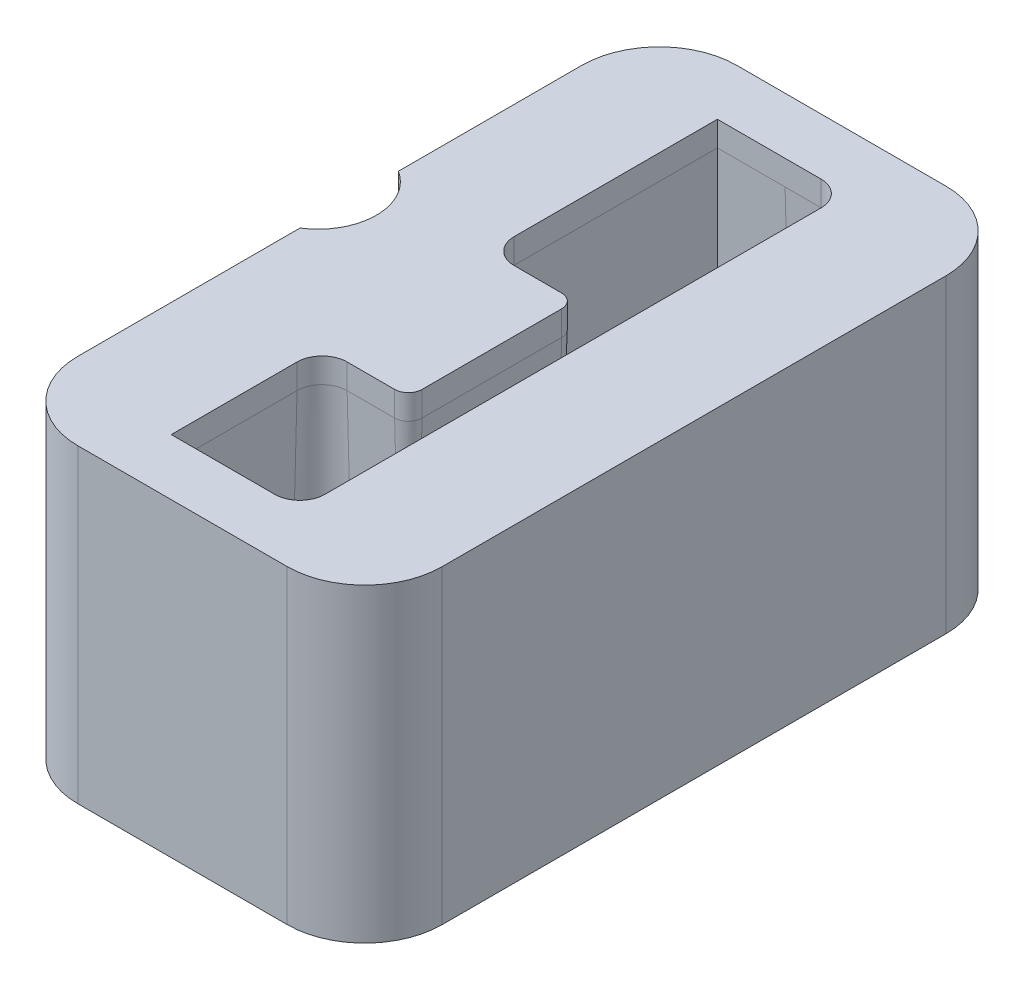
SolidWorks part; units mm, degrees
material "K110"
ref_plane "Front Plane" through (0, 0, 0) normal (0, 0, 1) x (1, 0, 0)
ref_plane "Top Plane" through (0, 0, 0) normal (0, 1, 0) x (1, 0, 0)
ref_plane "Right Plane" through (0, 0, 0) normal (1, 0, 0) x (0, 0, -1)
sketch "Sketch1" plane through (0, 0, 0) normal (0, 1, 0) x (1, 0, 0)
  line L1 (-23.5, -42.5) -> (23.5, -42.5)
  line L2 (-23.5, -42.5) -> (-23.5, 42.5)
  line L3 (-23.5, 42.5) -> (23.5, 42.5)
  line L4 (23.5, -42.5) -> (23.5, 42.5)
  line L5 (-23.5, -42.5) -> (23.5, 42.5) construction
  line L6 (-23.5, 42.5) -> (23.5, -42.5) construction
  point P0 (0, 0)
  dimension "D1" = 85
  dimension "D2" = 47
extrude "Boss-Extrude1" add sketch "Sketch1" against normal blind 40
fillet "Fillet1" radius 10 4 edges at (-23.5, -20, -42.5) (23.5, -20, -42.5) (-23.5, -20, 42.5) (23.5, -20, 42.5)
sketch "Sketch3" plane through (0, 0, 0) normal (0, 1, 0) x (1, 0, 0)
  line L88 (4.63, 35.23) -> (-8.73, 35.23)
  line L89 (-8.73, 35.23) -> (-8.73, 9)
  line L90 (-5.5, 5.77) -> (0.63, 5.77)
  line L91 (2.4, 4) -> (2.4, -14)
  line L92 (0.63, -15.77) -> (-5.5, -15.77)
  line L93 (-8.73, -19) -> (-8.73, -35.23)
  line L94 (-8.73, -35.23) -> (4.63, -35.23)
  line L95 (7.86, -32) -> (7.86, 32)
  line L96 (4.63, 35.23) -> (-8.73, 35.23)
  line L97 (-8.73, 35.23) -> (-8.73, 9)
  line L98 (-5.5, 5.77) -> (0.63, 5.77)
  line L99 (2.4, 4) -> (2.4, -14)
  line L100 (0.63, -15.77) -> (-5.5, -15.77)
  line L101 (-8.73, -19) -> (-8.73, -35.23)
  line L102 (-8.73, -35.23) -> (4.63, -35.23)
  line L103 (7.86, -32) -> (7.86, 32)
  arc A48 (7.86, 32) -> (4.63, 35.23) centre (4.63, 32) ccw
  arc A49 (-8.73, 9) -> (-5.5, 5.77) centre (-5.5, 9) ccw
  arc A50 (2.4, 4) -> (0.63, 5.77) centre (0.63, 4) ccw
  arc A51 (0.63, -15.77) -> (2.4, -14) centre (0.63, -14) ccw
  arc A52 (-5.5, -15.77) -> (-8.73, -19) centre (-5.5, -19) ccw
  arc A53 (4.63, -35.23) -> (7.86, -32) centre (4.63, -32) ccw
  arc A54 (7.86, 32) -> (4.63, 35.23) centre (4.63, 32) ccw
  arc A55 (-8.73, 9) -> (-5.5, 5.77) centre (-5.5, 9) ccw
  arc A56 (2.4, 4) -> (0.63, 5.77) centre (0.63, 4) ccw
  arc A57 (0.63, -15.77) -> (2.4, -14) centre (0.63, -14) ccw
  arc A58 (-5.5, -15.77) -> (-8.73, -19) centre (-5.5, -19) ccw
  arc A59 (4.63, -35.23) -> (7.86, -32) centre (4.63, -32) ccw
  dimension "D1" = 0.23
extrude "Cut-Extrude1" cut sketch "Sketch3" against normal up to next
sketch "Sketch4" plane through (0, 0, 0) normal (1, 0, 0) x (0, 0, -1)
  line L6 (35.23, -3.2) -> (36.1936, -40)
  line L7 (35.23, -40) -> (35.23, 0) construction
  line L9 (36.1936, -40) -> (35.23, -40)
  line L10 (35.23, -40) -> (35.23, -3.2)
  line L11 (25.85, 0) -> (-25.85, 0) construction
  dimension "D1" = 3.2
  dimension "D2" = 1.5
sketch "Sketch5" plane through (0, 0, 0) normal (0, 1, 0) x (1, 0, 0)
  line L16 (-8.73, -35.23) -> (4.63, -35.23) construction
  line L17 (-8.73, -19) -> (-8.73, -35.23) construction
  line L18 (0.63, -15.77) -> (-5.5, -15.77) construction
  line L19 (2.4, 4) -> (2.4, -14) construction
  line L20 (-5.5, 5.77) -> (0.63, 5.77) construction
  line L21 (-8.73, 35.23) -> (-8.73, 9) construction
  line L22 (4.63, 35.23) -> (-8.73, 35.23) construction
  line L23 (7.86, -32) -> (7.86, 32) construction
  line L24 (-8.73, -35.23) -> (4.63, -35.23)
  line L25 (-8.73, -19) -> (-8.73, -35.23)
  line L26 (0.63, -15.77) -> (-5.5, -15.77)
  line L27 (2.4, 4) -> (2.4, -14)
  line L28 (-5.5, 5.77) -> (0.63, 5.77)
  line L29 (-8.73, 35.23) -> (-8.73, 9)
  line L30 (4.63, 35.23) -> (-8.73, 35.23)
  line L31 (7.86, -32) -> (7.86, 32)
  arc A8 (4.63, -35.23) -> (7.86, -32) centre (4.63, -32) ccw construction
  arc A9 (-5.5, -15.77) -> (-8.73, -19) centre (-5.5, -19) ccw construction
  arc A10 (0.63, -15.77) -> (2.4, -14) centre (0.63, -14) ccw construction
  arc A11 (2.4, 4) -> (0.63, 5.77) centre (0.63, 4) ccw construction
  arc A12 (-8.73, 9) -> (-5.5, 5.77) centre (-5.5, 9) ccw construction
  arc A13 (7.86, 32) -> (4.63, 35.23) centre (4.63, 32) ccw construction
  arc A14 (4.63, -35.23) -> (7.86, -32) centre (4.63, -32) ccw
  arc A15 (-5.5, -15.77) -> (-8.73, -19) centre (-5.5, -19) ccw
  arc A16 (0.63, -15.77) -> (2.4, -14) centre (0.63, -14) ccw
  arc A17 (2.4, 4) -> (0.63, 5.77) centre (0.63, 4) ccw
  arc A18 (-8.73, 9) -> (-5.5, 5.77) centre (-5.5, 9) ccw
  arc A19 (7.86, 32) -> (4.63, 35.23) centre (4.63, 32) ccw
sweep "Cut-Sweep1" cut profiles "Sketch4" path "Sketch5"
hole_wizard "M6 Tapped Hole1" positions "Sketch8" profile "Sketch7" tap size "M6" standard "ISO"
sketch "Sketch8" plane through (0, -40, 0) normal (0, -1, 0) x (-1, 0, 0)
  line L0 (-13.5, 42.5) -> (13.5, 42.5) construction
  line L1 (-23.5, -32.5) -> (-23.5, 32.5) construction
  line L2 (23.5, 32.5) -> (23.5, -32.5) construction
  line L3 (13.5, -42.5) -> (-13.5, -42.5) construction
  point P0 (-16.5, 35.5)
  point P2 (16.5, 35.5)
  point P4 (16.5, -35.5)
  point P6 (-16.5, -35.5)
  dimension "D1" = 7
  dimension "D2" = 7
  dimension "D3" = 7
  dimension "D4" = 7
sketch "Sketch7" plane through (16.5, -40, -35.5) normal (1, 0, 0) x (0, 0, -1)
  line L0 (0, 0) -> (0, 18.5022)
  line L1 (0, 18.5022) -> (2.5, 17)
  line L2 (2.5, 17) -> (2.5, 0.525)
  line L3 (2.5, 0.525) -> (3.025, 0)
  line L5 (3.025, 0) -> (0, 0)
  line L6 (-2.5, 0.525) -> (-3.025, 0) construction
  line L10 (0, 18.5022) -> (-2.5, 17) construction
  line L11 (0, -6.35) -> (0, 107.95) construction
  dimension "Tap Drill Dia." = 5
  dimension "Tap Drill Depth" = 17
  dimension "Near C'Sink Dia." = 6.05
  dimension "Near C'Sink Angle" = 90
  dimension "Drill Angle" = 118
cosmetic thread "Hole Thread1" parameters "D1"=12, "D2"=6
cosmetic thread "Hole Thread2" parameters "D1"=12, "D2"=6
cosmetic thread "Hole Thread3" parameters "D1"=12, "D2"=6
cosmetic thread "Hole Thread4" parameters "D1"=12, "D2"=6
extrude "Cut-Extrude2" cut sketch "Sketch9" against normal through all
sketch "Sketch9" plane through (236.38, 0, 7.73) normal (0, 1, 0) x (1, 0, 0)
  circle A0 centre (-263.88, 10.23) radius 7.5
extrude "Cut-Extrude3" cut sketch "Sketch10" against normal blind 30
sketch "Sketch10" plane through (236.38, -40, 7.73) normal (0, -1, 0) x (1, 0, 0)
  circle A0 centre (-263.88, -10.23) radius 10
